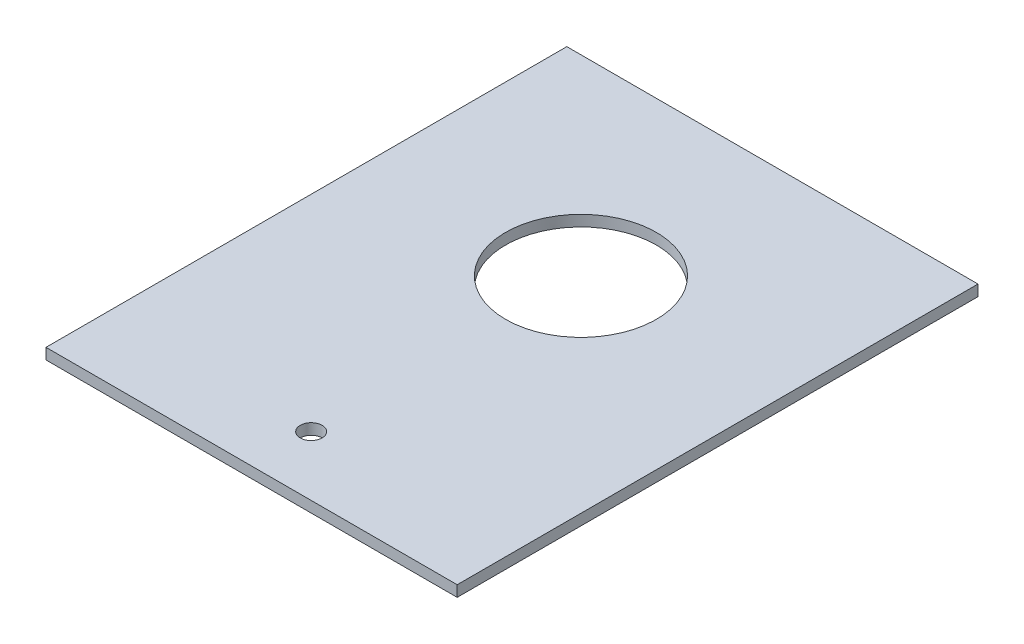
SolidWorks part; units mm, degrees
ref_plane "Front Plane" through (0, 0, 0) normal (0, 0, 1) x (1, 0, 0)
ref_plane "Top Plane" through (0, 0, 0) normal (0, 1, 0) x (1, 0, 0)
ref_plane "Right Plane" through (0, 0, 0) normal (1, 0, 0) x (0, 0, -1)
ref_plane "Plane1" through (0, 32, 0) normal (0, 1, 0) x (1, 0, 0)
sketch "Sketch1" plane through (0, 32, 0) normal (0, 1, 0) x (1, 0, 0)
  line L0 (75, 69.8429) -> (75, -120.1571) construction
  line L1 (-75, -120.1571) -> (75, -120.1571) construction
  line L2 (-75, 69.8429) -> (75, 69.8429) construction
  line L3 (-75, 69.8429) -> (-75, -120.1571) construction
  line L4 (75, 69.8429) -> (75, -120.1571)
  line L5 (-75, -120.1571) -> (75, -120.1571)
  line L6 (-75, 69.8429) -> (75, 69.8429)
  line L7 (-75, 69.8429) -> (-75, -120.1571)
extrude "Boss-Extrude1" add sketch "Sketch1" along normal blind 4
hole_wizard "Hole1" positions "Sketch2" profile "Sketch3" legacy
sketch "Sketch2" plane through (0, 36, 0) normal (0, 1, 0) x (1, 0, 0)
  point P0 (0, 0)
sketch "Sketch3" plane through (0, 36, 0) normal (1, 0, 0) x (0, 0, 1)
  line L0 (0, 0) -> (0, 100)
  line L1 (0, 100) -> (27.5, 100)
  line L2 (27.5, 100) -> (27.5, 0)
  line L3 (27.5, 0) -> (0, 0)
  line L4 (0, 110) -> (0, -10) construction
  dimension "Diameter" = 55
  dimension "Depth" = 100
hole_wizard "Hole2" positions "Sketch4" profile "Sketch5" legacy
sketch "Sketch4" plane through (0, 36, 0) normal (0, 1, 0) x (1, 0, 0)
  point P0 (0, -98.42)
sketch "Sketch5" plane through (0, 36, 98.42) normal (1, 0, 0) x (0, 0, 1)
  line L0 (0, 0) -> (0, 100)
  line L1 (0, 100) -> (4, 100)
  line L2 (4, 100) -> (4, 0)
  line L3 (4, 0) -> (0, 0)
  line L4 (0, 110) -> (0, -10) construction
  dimension "Diameter" = 8
  dimension "Depth" = 100
